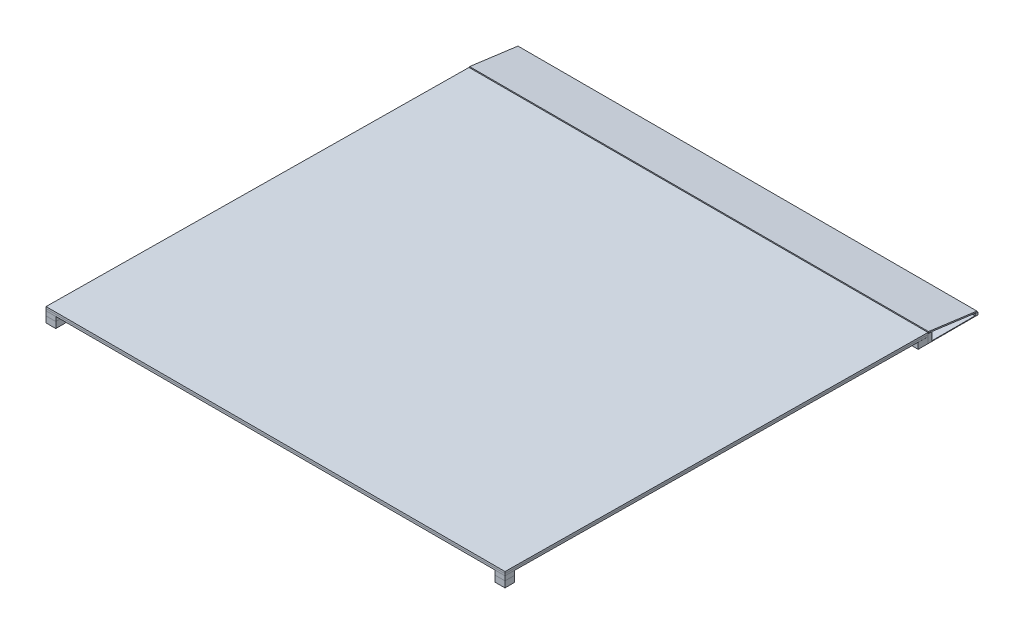
SolidWorks part; units mm, degrees
material "Pine"
ref_plane "Front" through (0, 0, 0) normal (0, 0, 1) x (1, 0, 0)
ref_plane "Top" through (0, 0, 0) normal (0, 1, 0) x (1, 0, 0)
ref_plane "Right" through (0, 0, 0) normal (1, 0, 0) x (0, 0, -1)
sketch "Sketch1" plane through (0, 0, 0) normal (0, 1, 0) x (1, 0, 0)
  line L1 (-2438.4, 2222.5) -> (2438.4, 2222.5) construction
  line L2 (-2438.4, 2222.5) -> (-2438.4, -2222.5) construction
  line L3 (-2438.4, -2222.5) -> (2438.4, -2222.5) construction
  line L4 (2438.4, 2222.5) -> (2438.4, -2222.5) construction
  line L5 (-2438.4, 2222.5) -> (2438.4, -2222.5) construction
  line L6 (-2438.4, -2222.5) -> (2438.4, 2222.5) construction
  point P0 (0, 0)
  dimension "D1" = 4876.8
  dimension "D2" = 4445
ref_plane "Plane1" through (0, 0, -2222.5) normal (0, 0, 1) x (1, 0, 0)
ref_plane "Plane2" through (0, 0, 2222.5) normal (0, 0, 1) x (1, 0, 0)
ref_plane "Plane3" through (-2438.4, 0, 0) normal (-1, 0, 0) x (0, 0, 1)
ref_plane "Plane4" through (2438.4, 0, 0) normal (-1, 0, 0) x (0, 0, 1)
sketch "Sketch2" plane through (2438.4, 0, 0) normal (-1, 0, 0) x (0, 0, 1)
  line L0 (-2178.05, 0) -> (-1015.9443, 12.17)
  line L1 (-2222.5, 0) -> (2222.5, 0) construction
  line L2 (-1015.9443, 12.17) -> (1015.9443, 33.4487)
  line L3 (1015.9443, 33.4487) -> (2222.5, 46.0841)
  line L4 (2222.5, -2682.24) -> (2222.5, 2682.24) construction
  line L5 (2222.5, 0) -> (-2222.5, 0) construction
  line L6 (0, 0) -> (0, 22.8093) construction
  line L7 (-2222.5, -2682.24) -> (-2222.5, 2682.24) construction
  dimension "D1" = 0.6
  dimension "D2" = 2032
  dimension "D3" = 4400.7913
  dimension "D4" = 44.45
  dimension "D5" = 46.0841
extrude "Extrude-Thin1" add sketch "Sketch2" along normal blind 4775.2 thin thin type one direction reverse wall 19.05
sketch "Sketch3" plane through (0, 0, 0) normal (0, 1, 0) x (1, 0, 0)
  line L13 (-2336.8, -2222.5) -> (-2235.2, -2222.5)
  line L14 (-2336.8, -2222.5) -> (-2336.8, -2120.9)
  line L15 (-2336.8, -2120.9) -> (-2235.2, -2120.9)
  line L16 (-2235.2, -2222.5) -> (-2235.2, -2120.9)
  line L21 (2438.4, -2222.5) -> (2336.8, -2222.5)
  line L22 (2438.4, -2222.5) -> (2438.4, -2120.9)
  line L23 (2438.4, -2120.9) -> (2336.8, -2120.9)
  line L24 (2336.8, -2222.5) -> (2336.8, -2120.9)
  dimension "D1" = 101.6
extrude "Boss-Extrude1" add sketch "Sketch3" along normal up to surface (46.0841 mm away) separate body up to face at (50.8, 23.0421, 22.225)
sketch "Sketch5" plane through (-2438.4, 0, 0) normal (-1, 0, 0) x (0, 0, 1)
  line L0 (-2222.5, 76.2) -> (-2222.5, 0)
  line L1 (-2222.5, -2682.24) -> (-2222.5, 2682.24) construction
  line L2 (2222.5, 0) -> (-2222.5, 0) construction
  line L3 (-2222.5, 0) -> (-2178.2495, 0)
  line L4 (-2178.2495, 0) -> (-2178.2495, 19.05)
  line L5 (-2178.2495, 19.05) -> (-2184.5995, 19.05)
  line L6 (-2184.5995, 19.05) -> (-2184.5995, 6.35)
  line L7 (-2184.5995, 6.35) -> (-2216.15, 6.35)
  line L8 (-2216.15, 6.35) -> (-2216.15, 76.2)
  line L9 (-2216.15, 76.2) -> (-2222.5, 76.2)
  line L10 (-2184.5995, 6.35) -> (-2184.5995, 0) construction
  dimension "D1" = 6.35
  dimension "D2" = 76.2
  dimension "D3" = 12.7
extrude "Boss-Extrude3" [suppressed] add sketch "Sketch5" against normal up to surface (4876.8 mm away) separate body up to face at (2438.4, 32.5665, 22.1253)
sketch "Sketch6" plane through (0, 0, 0) normal (0, -1, 0) x (1, 0, 0)
  line L1 (-2336.8, -2178.05) -> (-2235.2, -2178.05)
  line L2 (-2336.8, -2178.05) -> (-2336.8, -2076.45)
  line L3 (-2336.8, -2076.45) -> (-2235.2, -2076.45)
  line L4 (2438.4, 2120.9) -> (2438.4, 2222.5)
  line L5 (2438.4, 2222.5) -> (2336.8, 2222.5)
  line L6 (2336.8, 2222.5) -> (2336.8, 2120.9)
  line L7 (2336.8, 2120.9) -> (2438.4, 2120.9)
  line L8 (2438.4, 2120.9) -> (2438.4, 2222.5)
  line L9 (2438.4, 2222.5) -> (2336.8, 2222.5)
  line L10 (2336.8, 2222.5) -> (2336.8, 2120.9)
  line L11 (2336.8, 2120.9) -> (2438.4, 2120.9)
  line L12 (-2336.8, 2222.5) -> (-2336.8, 2120.9)
  line L13 (-2336.8, 2120.9) -> (-2235.2, 2120.9)
  line L14 (-2235.2, 2120.9) -> (-2235.2, 2222.5)
  line L15 (-2235.2, 2222.5) -> (-2336.8, 2222.5)
  line L16 (-2336.8, 2222.5) -> (-2336.8, 2120.9)
  line L17 (-2336.8, 2120.9) -> (-2235.2, 2120.9)
  line L18 (-2235.2, 2120.9) -> (-2235.2, 2222.5)
  line L19 (-2235.2, 2222.5) -> (-2336.8, 2222.5)
  line L20 (-2235.2, -2178.05) -> (-2235.2, -2076.45)
  line L21 (2438.4, -2178.05) -> (2336.8, -2178.05)
  line L22 (2438.4, -2178.05) -> (2438.4, -2076.45)
  line L23 (2438.4, -2076.45) -> (2336.8, -2076.45)
  line L24 (2336.8, -2178.05) -> (2336.8, -2076.45)
  dimension "D1" = 0
  dimension "D2" = 0
extrude "Boss-Extrude4" add sketch "Sketch6" along normal blind 63.5
sketch "Sketch8" plane through (0, 41.8558, -0.4383) normal (0, 0.9999, -0.0105) x (1, 0, 0)
  line L4 (2438.4, -2222.8607) -> (2438.4, 2177.9306)
  line L5 (2438.4, 2177.9306) -> (-2336.8, 2177.9306)
  line L6 (-2336.8, 2177.9306) -> (-2336.8, -2222.8607)
  line L7 (-2336.8, -2222.8607) -> (2438.4, -2222.8607)
  line L8 (2438.4, -2222.8607) -> (2438.4, 2177.9306)
  line L9 (2438.4, 2177.9306) -> (-2336.8, 2177.9306)
  line L10 (-2336.8, 2177.9306) -> (-2336.8, -2222.8607)
  line L11 (-2336.8, -2222.8607) -> (2438.4, -2222.8607)
  dimension "D1" = 0
extrude "Boss-Extrude5" add sketch "Sketch8" along normal blind 19.05 separate body
sketch "Sketch7" plane through (0, 0, -2178.05) normal (0, 0, -1) x (-1, 0, 0)
  line L5 (-2438.4, -63.5) -> (2336.8, -63.5)
  line L6 (-2438.4, -63.5) -> (-2438.4, 25.4)
  line L7 (-2438.4, 25.4) -> (2336.8, 25.4)
  line L8 (2336.8, -63.5) -> (2336.8, 25.4)
  dimension "D1" = 88.9
extrude "Boss-Extrude6" add sketch "Sketch7" along normal blind 38.1 separate body
sketch "Sketch9" plane through (0, 0, -2216.15) normal (0, 0, -1) x (-1, 0, 0)
  line L0 (2336.8, -63.5) -> (2336.8, 25.4) construction
  line L1 (-2438.4, -63.5) -> (2336.8, -63.5)
  line L2 (-2438.4, -63.5) -> (-2438.4, -38.1)
  line L3 (-2438.4, -38.1) -> (2336.8, -38.1)
  line L4 (2336.8, -63.5) -> (2336.8, -38.1)
  dimension "D1" = 25.4
extrude "Boss-Extrude8" add sketch "Sketch9" along normal blind 25.4 from offset 457.2 separate body
sketch "Sketch10" plane through (2438.4, 0, 0) normal (1, 0, 0) x (0, 0, -1)
  line L0 (2216.15, 25.4) -> (2216.15, -63.5)
  line L1 (2216.15, -63.5) -> (2673.35, -63.5)
  line L2 (2673.35, -63.5) -> (2673.35, -38.1)
  line L3 (2673.35, -38.1) -> (2667, -38.1)
  line L4 (2667, -38.1) -> (2667, -57.15)
  line L5 (2667, -57.15) -> (2222.5, -57.15)
  line L6 (2222.5, -57.15) -> (2222.5, 25.4)
  line L7 (2222.5, 25.4) -> (2216.15, 25.4)
  line L8 (2673.35, -38.1) -> (2673.35, -63.5) construction
  line L9 (2222.5, -57.15) -> (2222.5, -63.5) construction
  dimension "D1" = 6.35
extrude "Boss-Extrude9" add sketch "Sketch10" against normal up to vertex (4775.2 mm away) separate body up to point (-2336.8, 38.0979, -2178.449)
sketch "Sketch11" plane through (2438.4, 0, 0) normal (1, 0, 0) x (0, 0, -1)
  line L0 (2182.5062, 30.7325) -> (2686.05, -36.4067)
  line L1 (2686.05, -36.4067) -> (2687.7285, -23.8181)
  line L2 (2687.7285, -23.8181) -> (2184.1847, 43.3211)
  line L3 (2184.1847, 43.3211) -> (2182.5062, 30.7325)
  line L5 (2698.75, -38.1) -> (2698.75, -63.5) construction
  dimension "D1" = 12.7
  dimension "D2" = 508
  dimension "D3" = 12.7
extrude "Boss-Extrude10" add sketch "Sketch11" against normal up to vertex (4775.2 mm away) separate body up to point (-2336.8, -38.1, -2698.75)
